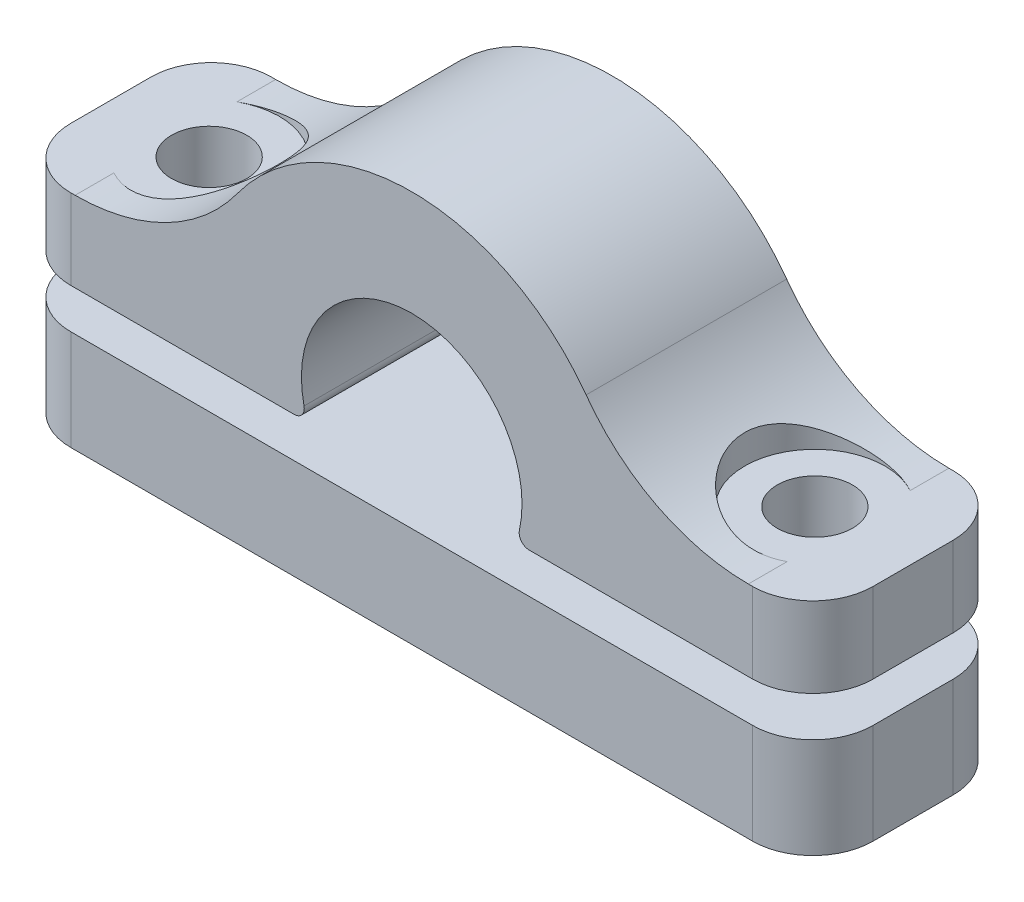
SolidWorks part; units mm, degrees
ref_plane "Front Plane" through (0, 0, 0) normal (0, 0, 1) x (1, 0, 0)
ref_plane "Top Plane" through (0, 0, 0) normal (0, 1, 0) x (1, 0, 0)
ref_plane "Right Plane" through (0, 0, 0) normal (1, 0, 0) x (0, 0, -1)
sketch "Sketch1" plane through (0, 0, 0) normal (0, 1, 0) x (1, 0, 0)
  line L1 (-20, 5) -> (20, 5)
  line L2 (-20, 5) -> (-20, -5)
  line L3 (-20, -5) -> (20, -5)
  line L4 (20, 5) -> (20, -5)
  line L5 (-20, 5) -> (20, -5) construction
  line L6 (-20, -5) -> (20, 5) construction
  point P0 (0, 0)
  dimension "D1" = 40
  dimension "D2" = 10
sketch "Sketch2" plane through (0, 0, 0) normal (0, 0, 1) x (1, 0, 0)
  line L0 (-4.7339, 0) -> (4.7339, 0) construction
  line L1 (0, -55) -> (0, 55) construction
  line L2 (-10.3789, 0) -> (10.3789, 0) construction
  line L3 (-10.3789, 0) -> (-4.7339, 0)
  line L4 (4.7339, 0) -> (10.3789, 0)
  arc A0 (-4.7339, 0) -> (4.7339, 0) centre (0, 2.8) cw
  arc A2 (-10.3789, 0) -> (10.3789, 0) centre (0, 2.8) cw
  point P3 (0, 2.8)
  point P4 (0, 0)
  point P5 (-4.7339, 0)
  point P6 (4.7339, 0)
  dimension "D4" = 10.75
  dimension "D1" = 2.8
  dimension "D2" = 5.5
  dimension "D3" = 5.5
extrude "Boss-Extrude1" add sketch "Sketch1" against normal blind 5 from offset 1 offset against normal yes
extrude "Boss-Extrude2" add sketch "Sketch2" along normal blind 5 and the other way blind 5
sketch "Sketch3" plane through (0, 0, 0) normal (0, 1, 0) x (1, 0, 0)
  line L0 (-10.75, -5) -> (10.75, -5) construction
  line L1 (-20, 5) -> (-10, 5)
  line L2 (-20, 5) -> (-20, -5)
  line L3 (-20, -5) -> (-10, -5)
  line L4 (-10, 5) -> (-10, -5)
  line L5 (0, -55) -> (0, 55) construction
  line L6 (20, -5) -> (10, -5)
  line L7 (20, 5) -> (20, -5)
  line L8 (20, 5) -> (10, 5)
  line L9 (10, 5) -> (10, -5)
  dimension "D1" = 10
extrude "Boss-Extrude3" add sketch "Sketch3" along normal blind 5
fillet "Fillet1" radius 3 4 edges at (20, 2.5, -5) (20, 2.5, 5) (-20, 2.5, -5) (-20, 2.5, 5)
fillet "Fillet2" radius 3 4 edges at (-20, -3.5, 5) (-20, -3.5, -5) (20, -3.5, 5) (20, -3.5, -5)
fillet "Fillet4" radius 10 2 edges at (10.5225, 5, 0) (-10.5225, 5, 0)
sketch "Sketch4" plane through (0, 0, 0) normal (0, 1, 0) x (1, 0, 0)
  line L0 (-10.7525, 0) -> (10.7525, 0) construction
  circle A0 centre (-15.1, 0) radius 1.875
  circle A1 centre (15.1, 0) radius 1.875
  dimension "D1" = 3.75
  dimension "D2" = 15.1
  dimension "D3" = 15.1
extrude "Cut-Extrude1" cut sketch "Sketch4" against normal through all both and the other way through all
sketch "Sketch5" plane through (0, 0, 0) normal (0, 1, 0) x (1, 0, 0)
  line L0 (0, -5.5) -> (0, 5.5) construction
  circle A0 centre (-15.1, 0) radius 3.5
  circle A1 centre (15.1, 0) radius 3.5
  dimension "D1" = 7
extrude "Cut-Extrude2" cut sketch "Sketch5" along normal blind 10 from offset 5
sketch "Sketch9" plane through (0, 0, 0) normal (0, 1, 0) x (1, 0, 0)
  line L1 (25.6287, -11.6641) -> (-21.4657, -11.6641)
  line L2 (25.6287, -11.6641) -> (25.6287, 11.6724)
  line L3 (25.6287, 11.6724) -> (-21.4657, 11.6724)
  line L4 (-21.4657, -11.6641) -> (-21.4657, 11.6724)
extrude "Cut-Extrude5" cut sketch "Sketch9" along normal blind 1
fillet "Fillet5" radius 0.5 2 edges at (-5.1971, 1, 0) (5.1971, 1, 0)
equation "\"shaftDiameter\"= 10mm"
equation "\"holeDiameter\"= 3.75mm"
equation "\"D1@Sketch4\"=\"holeDiameter\""
